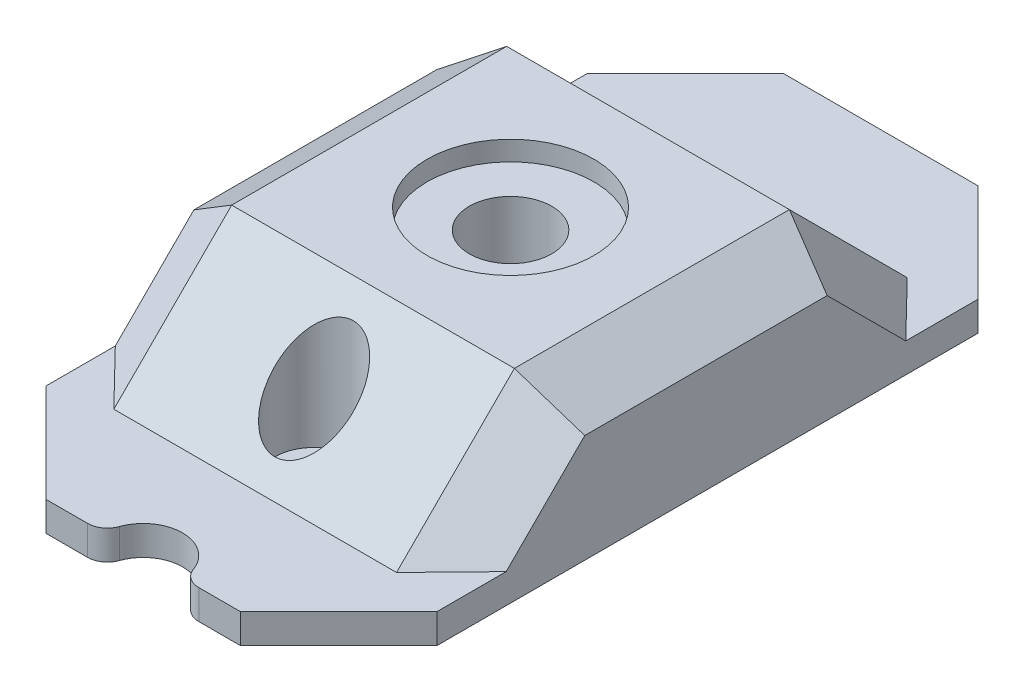
SolidWorks part; units mm, degrees
ref_plane "Front Plane" through (0, 0, 0) normal (0, 0, 1) x (1, 0, 0)
ref_plane "Top Plane" through (0, 0, 0) normal (0, 1, 0) x (1, 0, 0)
ref_plane "Right Plane" through (0, 0, 0) normal (1, 0, 0) x (0, 0, -1)
sketch "Sketch1" plane through (0, -561.2989, 0) normal (0, -1, 0) x (1, 0, 0)
  line L1 (-191.1108, 595.8201) -> (-171.3108, 595.8201)
  line L2 (-191.2108, 595.9201) -> (-171.2108, 595.9201)
  line L3 (-191.2108, 595.9201) -> (-191.2108, 540.6201)
  line L4 (-191.2108, 540.6201) -> (-171.2108, 540.6201)
  line L5 (-171.2108, 595.9201) -> (-171.2108, 540.6201)
  line L6 (-171.3108, 595.8201) -> (-171.3108, 540.7201)
  line L7 (-191.1108, 540.7201) -> (-171.3108, 540.7201)
  line L8 (-191.1108, 595.8201) -> (-191.1108, 540.7201)
  circle A0 centre (-181.2108, 588.4201) radius 1.7
  circle A1 centre (-181.2108, 548.4201) radius 1.7
  line M3 (-184.2109, 389.6201) -> (-184.2109, 789.6201)
  dimension "D1" = 3.4
  dimension "D3" = 3.4
  dimension "D2" = 0.1
extrude "Boss-Extrude1" add sketch "Sketch1" along normal blind 6 contours L7 L6 L1 A1 A0 M3 | L1 L8 L7 M3 region at (-187.6609, -561.2989, 568.2701) region at (-177.6704, -561.2989, 568.2662)
ref_plane "Plane1" through (0, -564.2989, 0) normal (0, 1, 0) x (1, 0, 0)
sketch "Sketch2" plane through (0, -564.2989, 0) normal (0, 1, 0) x (1, 0, 0)
  line L0 (-191.1108, -595.8201) -> (-191.1108, -540.7201) construction
  line L1 (-191.1108, -530.7201) -> (-171.3108, -530.7201)
  line L2 (-201.1108, -540.7201) -> (-201.1108, -595.8201)
  line L3 (-191.1108, -605.8201) -> (-171.3108, -605.8201)
  line L4 (-161.3108, -540.7201) -> (-161.3108, -595.8201)
  line L5 (-171.3108, -595.8201) -> (-171.3108, -540.7201) construction
  line L6 (-191.1108, -540.7201) -> (-171.3108, -540.7201) construction
  line L7 (-191.1108, -595.8201) -> (-171.3108, -595.8201) construction
  line L8 (-201.1108, -540.7201) -> (-191.1108, -530.7201)
  line L9 (-171.3108, -530.7201) -> (-161.3108, -540.7201)
  line L10 (-161.3108, -595.8201) -> (-171.3108, -605.8201)
  line L11 (-201.1108, -595.8201) -> (-191.1108, -605.8201)
  circle A0 centre (-181.2108, -548.4201) radius 2.1
  circle A1 centre (-181.2108, -588.4201) radius 2.1
  point P0 (-201.1108, -530.7201)
  point P1 (-161.3108, -605.8201)
  point P2 (-201.1108, -605.8201)
  point P3 (-161.3108, -530.7201)
  dimension "D1" = 10
  dimension "D2" = 10
  dimension "D3" = 10
  dimension "D4" = 10
extrude "Boss-Extrude2" add sketch "Sketch2" along normal up to vertex (3 mm away) up to point (-171.3108, -561.2989, 595.8201)
chamfer "Chamfer2" distance 3 angle 50 1 edges at (-191.1108, -567.2989, 568.2701) first distance on face at (-191.1108, -565.7989, 568.2701)
sketch "Sketch3" plane through (0, -561.2989, 0) normal (0, 1, 0) x (1, 0, 0)
  line L0 (-201.1108, -540.7201) -> (-201.1108, -595.8201) construction
  line L1 (-201.1108, -556.4201) -> (-161.3108, -556.4201)
  line L2 (-201.1108, -556.4201) -> (-201.1108, -580.4201)
  line L3 (-201.1108, -580.4201) -> (-161.3108, -580.4201)
  line L4 (-161.3108, -556.4201) -> (-161.3108, -580.4201)
  line L5 (-161.3108, -595.8201) -> (-161.3108, -540.7201) construction
  circle A0 centre (-181.2108, -548.4201) radius 1.7 construction
  circle A1 centre (-181.2108, -588.4201) radius 1.7 construction
  dimension "D1" = 8
  dimension "D2" = 8
extrude "Boss-Extrude3" add sketch "Sketch3" along normal blind 12
sketch "Sketch5" plane through (0, -549.2989, 0) normal (0, 1, 0) x (1, 0, 0)
  line L0 (-181.2108, -556.4201) -> (-181.2108, -580.4201) construction
  line L1 (-161.3108, -556.4201) -> (-201.1108, -556.4201) construction
  line L2 (-201.1108, -580.4201) -> (-161.3108, -580.4201) construction
  circle A0 centre (-181.2108, -568.4201) radius 4.2
  dimension "D1" = 8.4
extrude "Cut-Extrude2" cut sketch "Sketch5" against normal blind 34
sketch "Sketch7" plane through (0, -561.2989, 0) normal (0, 1, 0) x (1, 0, 0)
  circle A0 centre (-181.2108, -548.4201) radius 4
  circle A1 centre (-181.2108, -588.4201) radius 4
extrude "Cut-Extrude4" cut sketch "Sketch7" against normal blind 2
sketch "Sketch10" plane through (0, -561.2989, 0) normal (0, 1, 0) x (1, 0, 0)
  line L0 (-191.1108, -605.8201) -> (-171.3108, -605.8201) construction
  circle A0 centre (-181.2108, -605.8201) radius 4
  dimension "D1" = 8
extrude "Cut-Extrude5" cut sketch "Sketch10" against normal blind 6
fillet "Fillet2" radius 2 2 edges at (-177.2108, -562.7989, 605.8201) (-185.2108, -562.7989, 605.8201)
sketch "Sketch11" plane through (0, -567.2989, 0) normal (0, -1, 0) x (1, 0, 0)
  line L0 (-187.5356, 595.8201) -> (-171.3108, 595.8201) construction
  line L1 (-185.0214, 575.0201) -> (-188.8319, 568.4201)
  line L2 (-188.8319, 568.4201) -> (-185.0214, 561.8201)
  line L3 (-185.0214, 561.8201) -> (-177.4003, 561.8201)
  line L4 (-177.4003, 561.8201) -> (-173.5898, 568.4201)
  line L5 (-173.5898, 568.4201) -> (-177.4003, 575.0201)
  line L6 (-177.4003, 575.0201) -> (-185.0214, 575.0201)
  circle A0 centre (-181.2108, 568.4201) radius 6.6 construction
  dimension "D1" = 13.2
  dimension "D2" = 0
extrude "Cut-Extrude6" cut sketch "Sketch11" against normal blind 5.4
chamfer "Chamfer3" distance 14 angle 45 2 edges at (-181.2108, -561.2989, 580.4201) (-181.2108, -561.2989, 556.4201)
chamfer "Chamfer4" distance 4 angle 54 6 edges at (-201.1108, -555.2989, 548.4201) (-201.1108, -555.2989, 588.4201) (-201.1108, -549.2989, 568.4201) (-161.3108, -555.2989, 588.4201) (-161.3108, -555.2989, 548.4201) (-161.3108, -549.2989, 568.4201) first distance on face at (-201.1108, -559.0489, 568.3451) first distance on face at (-161.3108, -559.0489, 568.3451)
sketch "Sketch12" plane through (0, -549.2989, 0) normal (0, 1, 0) x (1, 0, 0)
  circle A0 centre (-181.2108, -568.4201) radius 8.5
  dimension "D1" = 17
extrude "Cut-Extrude7" cut sketch "Sketch12" against normal blind 2
